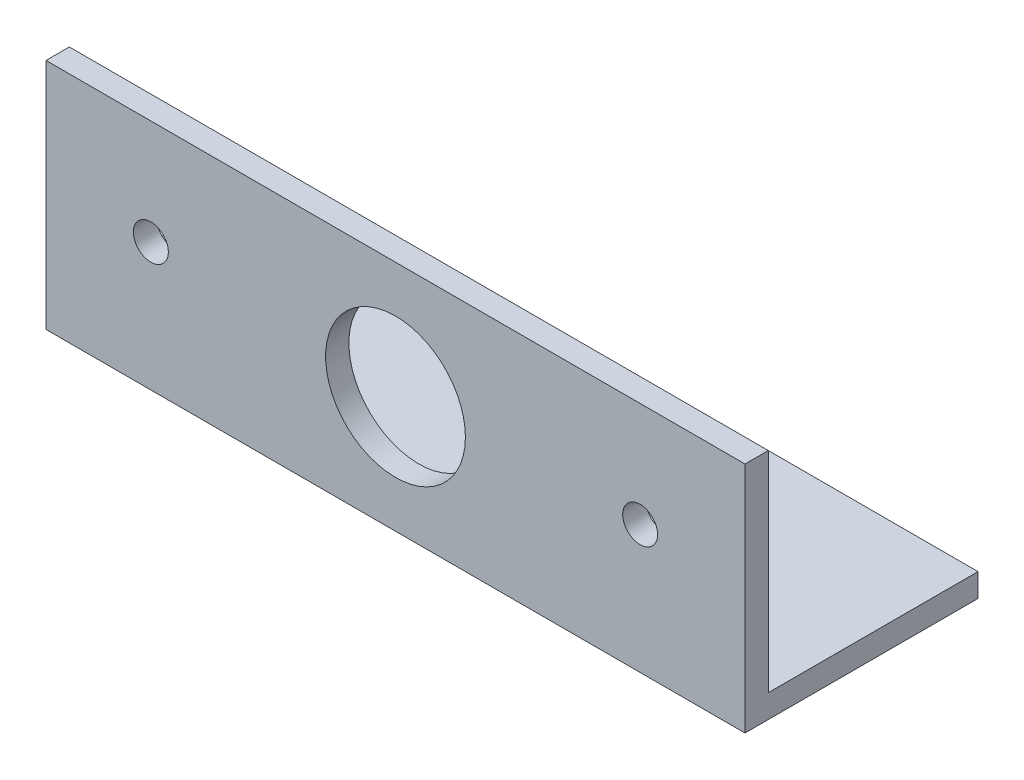
SolidWorks part; units mm, degrees
ref_plane "Front Plane" through (0, 0, 0) normal (0, 0, 1) x (1, 0, 0)
ref_plane "Top Plane" through (0, 0, 0) normal (0, 1, 0) x (1, 0, 0)
ref_plane "Right Plane" through (0, 0, 0) normal (1, 0, 0) x (0, 0, -1)
sketch "Sketch1" plane through (0, 0, 0) normal (1, 0, 0) x (0, 0, -1)
  line L0 (0, 20) -> (0, 0)
  line L1 (0, 0) -> (20, 0)
  line L2 (20, 0) -> (20, 2)
  line L3 (20, 2) -> (2, 2)
  line L4 (2, 2) -> (2, 20)
  line L5 (0, 20) -> (2, 20)
  dimension "D1" = 20
  dimension "D2" = 20
  dimension "D3" = 2
  dimension "D4" = 2
extrude "Boss-Extrude1" add sketch "Sketch1" along normal blind 30 and the other way blind 30
sketch "Sketch2" plane through (0, 0, 0) normal (0, 0, 1) x (1, 0, 0)
  line L0 (-30, 10) -> (30, 10) construction
  line L1 (-30, 20) -> (-30, 0) construction
  line L2 (30, 20) -> (30, 0) construction
  line L3 (-30, 20) -> (30, 20) construction
  line L4 (-21, 11) -> (21, 11) construction
  circle A0 centre (-21, 11) radius 1.5
  circle A1 centre (21, 11) radius 1.5
  circle A2 centre (0, 10) radius 6
  dimension "D3" = 3
  dimension "D4" = 9
  dimension "D5" = 12
  dimension "D2" = 9
  dimension "D1" = 42
extrude "Cut-Extrude1" cut sketch "Sketch2" against normal blind 2
